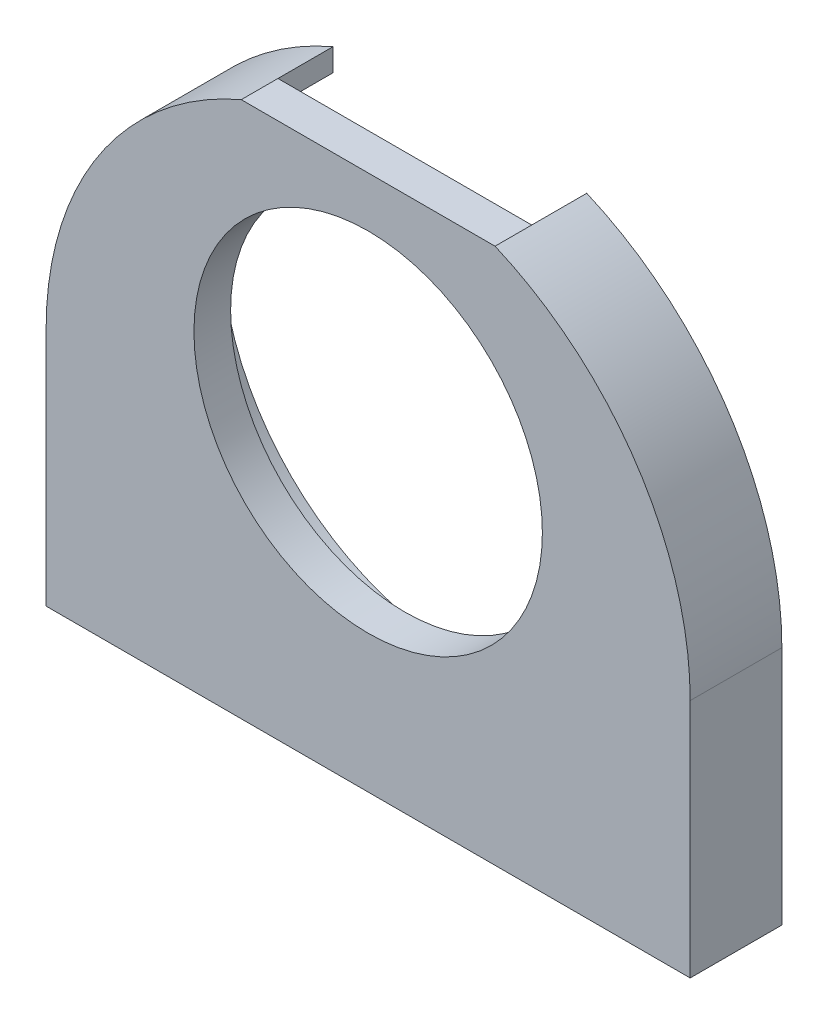
SolidWorks part; units mm, degrees
ref_plane "Front Plane" through (0, 0, 0) normal (0, 0, 1) x (1, 0, 0)
ref_plane "Top Plane" through (0, 0, 0) normal (0, 1, 0) x (1, 0, 0)
ref_plane "Right Plane" through (0, 0, 0) normal (1, 0, 0) x (0, 0, -1)
sketch "Sketch1" plane through (0, 0, 0) normal (0, 0, 1) x (1, 0, 0)
  line L0 (5.32, 14.0026) -> (5.32, 14.6195)
  line L1 (0, 0) -> (17.56, 0)
  line L2 (0, 0) -> (0, 6.55)
  line L3 (0, 6.55) -> (17.56, 6.55)
  line L4 (17.56, 0) -> (17.56, 6.55)
  line L6 (12.24, 14.0026) -> (12.24, 14.6195)
  arc A0 (5.32, 14.6195) -> (0, 6.55) centre (8.78, 6.55) ccw
  arc A1 (5.32, 14.0026) -> (12.24, 14.0026) centre (8.78, 8.5) ccw
  arc A2 (17.56, 6.55) -> (12.24, 14.6195) centre (8.78, 6.55) ccw
  dimension "D4" = 13
  dimension "D1" = 17.56
  dimension "D2" = 6.55
  dimension "D5" = 1.95
  dimension "D6" = 5.32
extrude "Boss-Extrude1" add sketch "Sketch1" along normal blind 1.5 contours A1 L3 L2 L1 L4 | A1 L0 A0 L3 | L3 A2 L6 A1 region at (1.98, 9.9073, 0) region at (8.78, 1.8126, 0) region at (15.58, 9.9073, 0)
sketch "Sketch3" plane through (0, 0, 1.5) normal (0, 0, 1) x (1, 0, 0)
  line L5 (5.32, 14.0026) -> (5.32, 14.6195)
  line L6 (0, 6.55) -> (0, 0)
  line L7 (0, 0) -> (17.56, 0)
  line L8 (17.56, 0) -> (17.56, 6.55)
  line L9 (12.24, 14.6195) -> (12.24, 14.0026)
  line L10 (5.32, 14.0026) -> (5.32, 14.6195)
  line L11 (0, 6.55) -> (0, 0)
  line L12 (0, 0) -> (17.56, 0)
  line L13 (17.56, 0) -> (17.56, 6.55)
  line L14 (12.24, 14.6195) -> (12.24, 14.0026)
  line L15 (0, 0) -> (17.56, 0)
  line L16 (17.56, 6.55) -> (17.56, 0)
  line L17 (0, 0) -> (0, 6.55)
  line L18 (5.32, 14.6195) -> (12.24, 14.6195)
  arc A3 (5.32, 14.0026) -> (12.24, 14.0026) centre (8.78, 8.5) ccw
  arc A4 (5.32, 14.6195) -> (0, 6.55) centre (8.78, 6.55) ccw
  arc A5 (17.56, 6.55) -> (12.24, 14.6195) centre (8.78, 6.55) ccw
  arc A6 (5.32, 14.0026) -> (12.24, 14.0026) centre (8.78, 8.5) ccw
  arc A7 (5.32, 14.6195) -> (0, 6.55) centre (8.78, 6.55) ccw
  arc A8 (17.56, 6.55) -> (12.24, 14.6195) centre (8.78, 6.55) ccw
  arc A9 (17.56, 6.55) -> (12.24, 14.6195) centre (8.78, 6.55) ccw
  arc A10 (0, 6.55) -> (5.32, 14.6195) centre (8.78, 6.55) cw
  arc M9 (12.24, 14.0026) -> (5.32, 14.0026) centre (8.78, 8.5) cw
  line M10 (5.32, 14.0026) -> (5.32, 14.6195)
  arc M11 (5.32, 14.6195) -> (0, 6.55) centre (8.78, 6.55) ccw
  line M12 (0, 6.55) -> (0, 0)
  line M13 (0, 0) -> (17.56, 0)
  line M14 (17.56, 0) -> (17.56, 6.55)
  arc M15 (17.56, 6.55) -> (12.24, 14.6195) centre (8.78, 6.55) ccw
  line M16 (12.24, 14.6195) -> (12.24, 14.0026)
  dimension "D1" = 0
extrude "Boss-Extrude2" add sketch "Sketch3" along normal blind 1 contours M16 M9 M10 M11 M12 M13 M14 M15 | L18 M10 M9 M16 region at (8.78, 1.7715, 1.5) region at (8.78, 8.4788, 1.5)
sketch "Sketch4" plane through (0, 0, 1.5) normal (0, 0, -1) x (-1, 0, 0)
  circle A0 centre (-8.78, 8.5) radius 4.75
  dimension "D1" = 9.5
extrude "Cut-Extrude1" cut sketch "Sketch4" against normal through all
